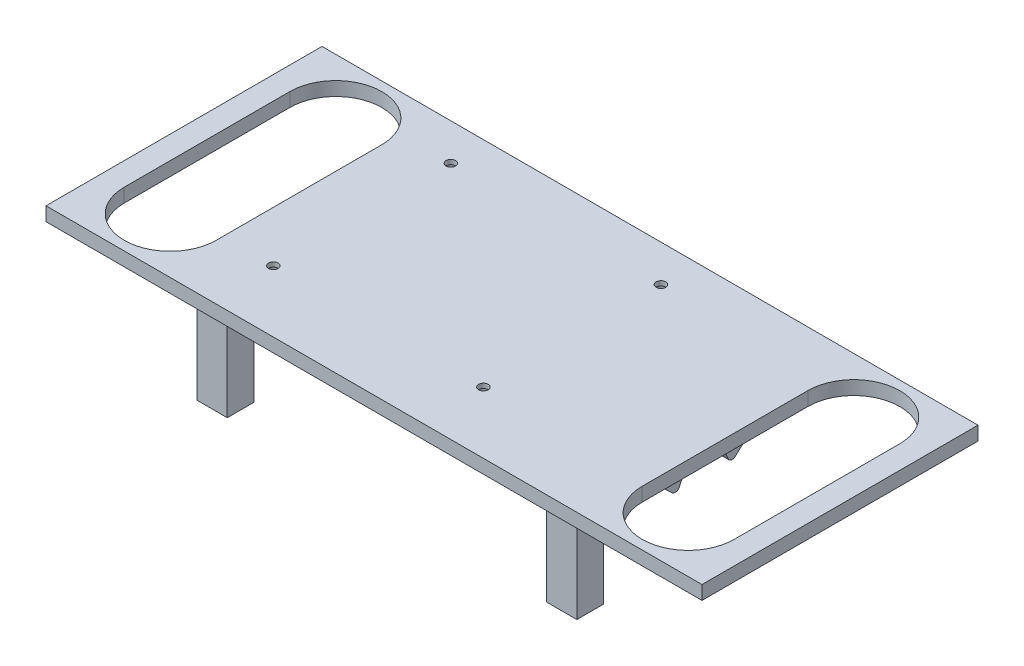
SolidWorks part; units mm, degrees
ref_plane "Front Plane" through (0, 0, 0) normal (0, 0, 1) x (1, 0, 0)
ref_plane "Top Plane" through (0, 0, 0) normal (0, 1, 0) x (1, 0, 0)
ref_plane "Right Plane" through (0, 0, 0) normal (1, 0, 0) x (0, 0, -1)
sketch "Sketch1" plane through (0, 0, 0) normal (0, 1, 0) x (1, 0, 0)
  line L0 (-5.842, 0) -> (-7.112, -1.2443)
  line L1 (-7.112, -1.2443) -> (-7.112, -8.6103)
  line L2 (-7.112, -8.6103) -> (1.27, -8.6103)
  line L3 (1.27, -8.6103) -> (1.27, -1.2443)
  line L4 (1.27, -1.2443) -> (0, 0)
  line L5 (0, 0) -> (-5.842, 0)
  line L6 (90.678, 0) -> (89.408, -1.2443)
  line L7 (89.408, -1.2443) -> (89.408, -8.6103)
  line L8 (89.408, -8.6103) -> (97.79, -8.6103)
  line L9 (97.79, -8.6103) -> (97.79, -1.2443)
  line L10 (97.79, -1.2443) -> (96.52, 0)
  line L11 (96.52, 0) -> (90.678, 0)
  point P2 (93.599, -8.6103)
  point P21 (-2.921, -8.6103)
  dimension "D1" = 7.366
  dimension "D2" = 8.382
  dimension "D3" = 1.778
  dimension "D4" = 5.842
  dimension "D5" = 96.52
extrude "Guide rods" add sketch "Sketch1" along normal blind 25.4
sketch "Sketch2" plane through (0, 25.4, 0) normal (0, 1, 0) x (1, 0, 0)
  line L0 (-7.112, -1.2443) -> (-7.112, -8.6103) construction
  line L1 (-45.212, -12.1663) -> (135.89, -12.1663)
  line L2 (-45.212, -12.1663) -> (-45.212, 64.0337)
  line L3 (-45.212, 64.0337) -> (135.89, 64.0337)
  line L4 (135.89, -12.1663) -> (135.89, 64.0337)
  line L5 (-7.112, -8.6103) -> (1.27, -8.6103) construction
  line L6 (97.79, -8.6103) -> (97.79, -1.2443) construction
  dimension "D1" = 38.1
  dimension "D2" = 3.556
  dimension "D3" = 38.1
  dimension "D4" = 76.2
extrude "baseplate" add sketch "Sketch2" along normal blind 3.81
sketch "Sketch4" plane through (0, 29.21, 0) normal (0, 1, 0) x (1, 0, 0)
  line L0 (-26.162, 48.7937) -> (-26.162, 3.0737) construction
  line L1 (-13.462, 48.7937) -> (-13.462, 3.0737)
  line L2 (-38.862, 48.7937) -> (-38.862, 3.0737)
  line L3 (-45.212, 64.0337) -> (-45.212, -12.1663) construction
  line L5 (-45.212, -12.1663) -> (135.89, -12.1663) construction
  line L6 (135.89, 64.0337) -> (-45.212, 64.0337) construction
  line L7 (45.339, 64.0337) -> (45.339, -12.1663) construction
  line L8 (116.84, 48.7937) -> (116.84, 3.0737) construction
  line L9 (104.14, 48.7937) -> (104.14, 3.0737)
  line L10 (129.54, 48.7937) -> (129.54, 3.0737)
  arc A0 (-13.462, 48.7937) -> (-38.862, 48.7937) centre (-26.162, 48.7937) ccw
  arc A1 (-38.862, 3.0737) -> (-13.462, 3.0737) centre (-26.162, 3.0737) ccw
  arc A2 (104.14, 48.7937) -> (129.54, 48.7937) centre (116.84, 48.7937) cw
  arc A3 (129.54, 3.0737) -> (104.14, 3.0737) centre (116.84, 3.0737) cw
  point P2 (-26.162, 25.9337)
  point P17 (116.84, 25.9337)
  dimension "D1" = 15.24
  dimension "D2" = 25.4
  dimension "D3" = 6.35
  dimension "D4" = 15.24
extrude "Handles" cut sketch "Sketch4" against normal through all
sketch "Sketch5" plane through (0, 29.21, 0) normal (0, 1, 0) x (1, 0, 0)
  line L0 (-45.212, 64.0337) -> (-45.212, -12.1663) construction
  line L5 (0.508, 53.8737) -> (0.508, 4.8737) construction
  line L6 (135.89, 64.0337) -> (-45.212, 64.0337) construction
  circle A0 centre (0.508, 53.8737) radius 1.325
  circle A1 centre (0.508, 4.8737) radius 1.325
  circle A2 centre (58.508, 53.8737) radius 1.325
  circle A3 centre (58.508, 4.8737) radius 1.325
  point P10 (-45.212, 25.9337)
  point P11 (0, 0)
  point P12 (0.508, 29.3737)
  dimension "D3" = 2.65
  dimension "D1" = 58
  dimension "D2" = 49
  dimension "D4" = 10.16
  dimension "D5" = 45.72
extrude "Screw Holes" cut sketch "Sketch5" against normal through all contours A2 | A3 | A0 | A1
sketch "Sketch6" plane through (135.89, 0, 0) normal (1, 0, 0) x (0, 0, -1)
  line L0 (27.686, 14.2875) -> (20.701, 14.2875) construction
  line L2 (-12.1663, 25.4) -> (64.0337, 25.4) construction
  line L4 (17.78, 25.4) -> (31.115, 25.4)
  line L6 (20.701, 14.2875) -> (8.636, 25.4)
  line L7 (8.636, 25.4) -> (46.736, 25.4)
  line L8 (46.736, 25.4) -> (34.671, 14.2875)
  line L9 (0, 25.4) -> (0, 0) construction
  arc A0 (34.671, 14.2875) -> (20.701, 14.2875) centre (27.686, 14.2875) ccw
  point P6 (27.686, 21.2725)
  line M8 (-12.1663, 25.4) -> (64.0337, 25.4)
  dimension "D2" = 13.97
  dimension "D1" = 27.686
  dimension "D3" = 11.1125
  dimension "D4" = 38.1
extrude "Axle Guide" add sketch "Sketch6" against normal up to surface (149.352 mm away) from surface contours A0 L8 L6 M8 region at (135.89, 21.9453, -27.686) up to face at (-13.462, 27.305, -25.9337) starting at face at (104.14, 27.305, -25.9337)
fillet "Fillet1" radius 1.27 2 edges at (45.339, 14.2875, -20.701) (45.339, 14.2875, -34.671)
sketch "Sketch7" plane through (0, 0, -64.0337) normal (0, 0, -1) x (-1, 0, 0)
  line L0 (-104.14, 15.5478) -> (13.462, 15.5478) construction
  line L1 (-104.14, 25.4) -> (-96.52, 25.4)
  line L2 (-104.14, 25.4) -> (-104.14, 15.5478)
  line L3 (-104.14, 15.5478) -> (-96.52, 15.5478)
  line L4 (-96.52, 25.4) -> (-96.52, 15.5478)
  line L5 (13.462, 25.4) -> (-104.14, 25.4) construction
  line L6 (13.462, 25.4) -> (5.842, 25.4)
  line L7 (13.462, 25.4) -> (13.462, 15.5478)
  line L8 (13.462, 15.5478) -> (5.842, 15.5478)
  line L9 (5.842, 25.4) -> (5.842, 15.5478)
  line L20 (-77.47, 25.4) -> (-13.208, 25.4)
  line L25 (-77.47, 25.4) -> (-77.47, 15.5478)
  line L26 (-77.47, 15.5478) -> (-13.208, 15.5478)
  line L27 (-13.208, 25.4) -> (-13.208, 15.5478)
  dimension "D1" = 7.62
  dimension "D2" = 19.05
  dimension "D3" = 19.05
extrude "Axle Guide Cut" cut sketch "Sketch7" against normal up to surface (64.0337 mm away) up to face at (93.599, 12.7, 0)
sketch "Sketch8" plane through (0, 25.4, 0) normal (0, -1, 0) x (1, 0, 0)
  circle A0 centre (0.508, -53.8737) radius 2.5
  circle A1 centre (58.508, -53.8737) radius 2.5
  circle A2 centre (58.508, -4.8737) radius 2.5
  circle A3 centre (0.508, -4.8737) radius 2.5
  circle M34 centre (58.508, -4.8737) radius 1.325
  circle M35 centre (58.508, -53.8737) radius 1.325
  circle M36 centre (0.508, -53.8737) radius 1.325
  dimension "D1" = 5
extrude "Countersink" cut sketch "Sketch8" against normal blind 2.54 contours A0 M36 | A1 M35 | A2 M34 | A3 region at (-1.9213, 25.4, -53.8737) region at (56.0787, 25.4, -53.8737) region at (56.0787, 25.4, -4.8737)
